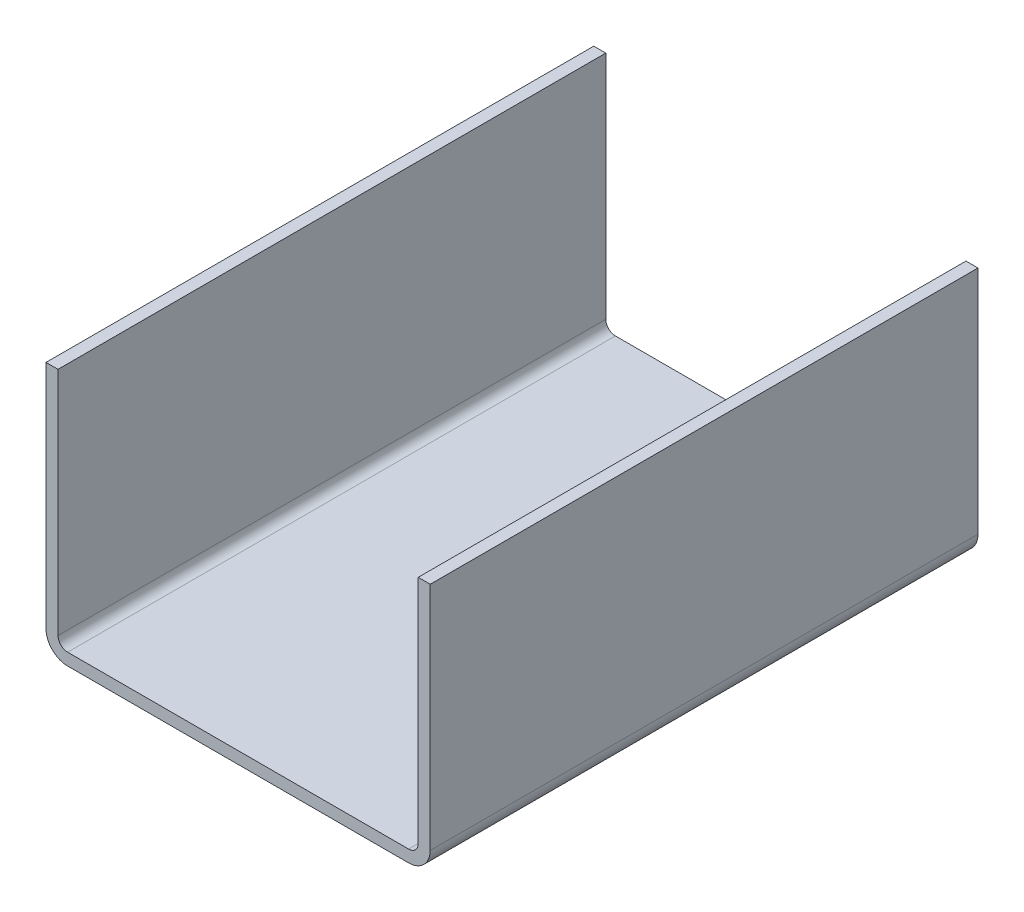
SolidWorks part; units mm, degrees
material "1060 Alloy"
ref_plane "Front Plane" through (0, 0, 0) normal (0, 0, 1) x (1, 0, 0)
ref_plane "Top Plane" through (0, 0, 0) normal (0, 1, 0) x (1, 0, 0)
ref_plane "Right Plane" through (0, 0, 0) normal (1, 0, 0) x (0, 0, -1)
sketch "Sketch1" plane through (0, 0, 0) normal (0, 0, 1) x (1, 0, 0)
  line L0 (1.016, 0) -> (37.084, 0)
  line L1 (0, 1.016) -> (0, 25.4)
  line L2 (38.1, 1.016) -> (38.1, 25.4)
  arc A0 (38.1, 1.016) -> (37.084, 0) centre (37.084, 1.016) cw
  arc A1 (0, 1.016) -> (1.016, 0) centre (1.016, 1.016) ccw
  point P8 (38.1, 0)
  point P11 (0, 0)
  dimension "D3" = 1.016
  dimension "D1" = 38.1
  dimension "D2" = 25.4
extrude "Extrude-Thin1" add sketch "Sketch1" along normal up to surface (57.9355 mm away) thin thin type one direction wall 1.27
